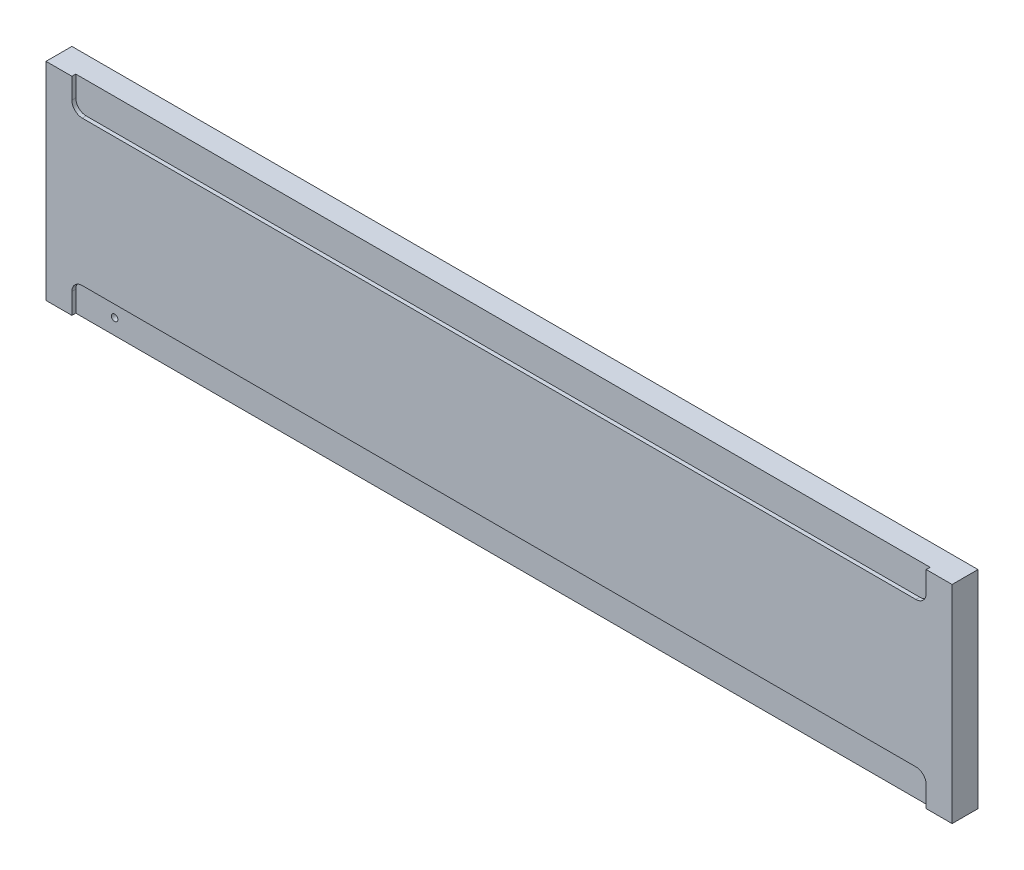
SolidWorks part; units mm, degrees
ref_plane "Alzado" through (0, 0, 0) normal (0, 0, 1) x (1, 0, 0)
ref_plane "Planta" through (0, 0, 0) normal (0, 1, 0) x (1, 0, 0)
ref_plane "Vista lateral" through (0, 0, 0) normal (1, 0, 0) x (0, 0, -1)
sketch "Croquis1" plane through (0, 0, 0) normal (0, 0, 1) x (1, 0, 0)
  line L1 (350, 80) -> (0, 80)
  line L2 (350, 80) -> (350, 0)
  line L3 (350, 0) -> (0, 0)
  line L4 (0, 80) -> (0, 0)
  dimension "D1" = 80
  dimension "D2" = 350
extrude "Saliente-Extruir1" add sketch "Croquis1" along normal blind 10
sketch "Croquis2" plane through (0, 0, 10) normal (0, 0, 1) x (1, 0, 0)
  line L1 (10, 80) -> (340, 80)
  line L3 (14, 68) -> (336, 68)
  line L5 (10, 0) -> (340, 0)
  line L7 (14, 12) -> (336, 12)
  line L10 (10, 80) -> (10, 72)
  line L11 (350, 80) -> (0, 80) construction
  line L12 (340, 80) -> (340, 72)
  line L13 (10, 0) -> (10, 8)
  line L14 (340, 8) -> (340, 0)
  arc A2 (10, 72) -> (14, 68) centre (14, 72) ccw
  arc A3 (336, 68) -> (340, 72) centre (336, 72) ccw
  arc A4 (14, 12) -> (10, 8) centre (14, 8) ccw
  arc A5 (340, 8) -> (336, 12) centre (336, 8) ccw
  dimension "D3" = 12
  dimension "D1" = 8
  dimension "D5" = 8
  dimension "D2" = 8
  dimension "D9" = 8
  dimension "D4" = 10
  dimension "D6" = 10
  dimension "D7" = 10
  dimension "D8" = 12
  dimension "D10" = 10
extrude "Cortar-Extruir1" cut sketch "Croquis2" against normal blind 1.5
hole_wizard "Taladro roscado M31" positions "Croquis3" profile "Croquis4" tap size "M3" standard "DIN"
sketch "Croquis3" plane through (0, 0, 8.5) normal (0, 0, 1) x (1, 0, 0)
  line L0 (0, 80) -> (0, 0) construction
  line L1 (10, 0) -> (340, 0) construction
  point P0 (25, 6)
  dimension "D1" = 25
  dimension "D2" = 6
cosmetic thread "Rosca de taladro1" parameters "D1"=6, "D2"=3
sketch "Croquis4" plane through (25, 6, 8.5) normal (1, 0, 0) x (0, -1, 0)
  line L0 (0, 0) -> (0, 7.7511)
  line L1 (0, 7.7511) -> (1.25, 7)
  line L2 (1.25, 7) -> (1.25, 0)
  line L5 (1.25, 0) -> (0, 0)
  line L10 (0, 7.7511) -> (-1.25, 7) construction
  line L11 (0, -6.35) -> (0, 107.95) construction
  dimension "Diámetro de perforador para roscar" = 2.5
  dimension "Profundidad de perforador para roscar" = 7
  dimension "Ángulo de perforador" = 118
